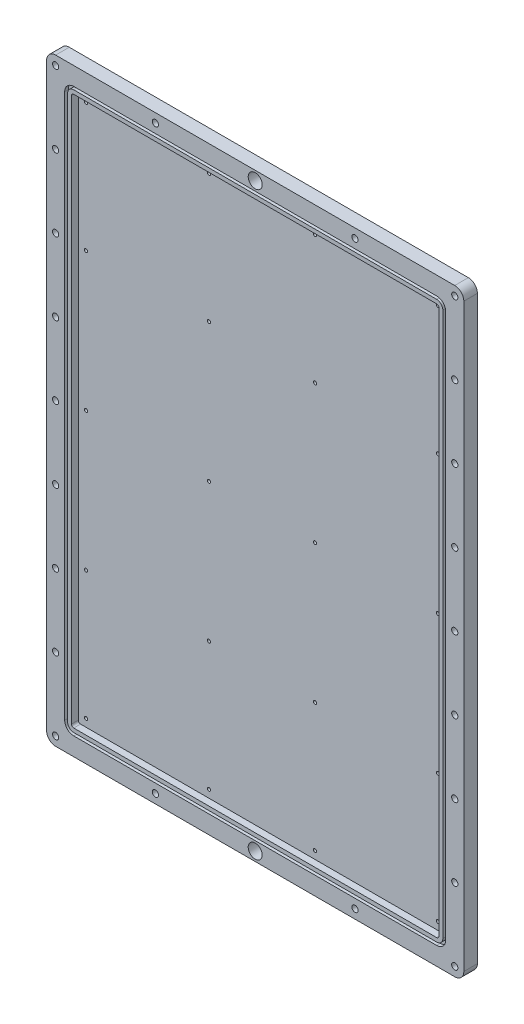
SolidWorks part; units mm, degrees
ref_plane "Front Plane" through (0, 0, 0) normal (0, 0, 1) x (1, 0, 0)
ref_plane "Top Plane" through (0, 0, 0) normal (0, 1, 0) x (1, 0, 0)
ref_plane "Right Plane" through (0, 0, 0) normal (1, 0, 0) x (0, 0, -1)
sketch "Sketch1" plane through (0, 0, 0) normal (0, 0, 1) x (1, 0, 0)
  line L1 (0, 0) -> (292.0492, 0)
  line L2 (0, 0) -> (0, 419.0492)
  line L3 (0, 419.0492) -> (292.0492, 419.0492)
  line L4 (292.0492, 0) -> (292.0492, 419.0492)
  dimension "D1" = 419.0492
  dimension "D2" = 292.0492
extrude "Boss-Extrude1" add sketch "Sketch1" along normal blind 9.525
sketch "Sketch4" plane through (0, 0, 9.525) normal (0, 0, 1) x (1, 0, 0)
  line L0 (91.477, 6.3246) -> (91.477, 0) construction
  line L1 (0, 0) -> (292.0492, 0) construction
  line L2 (6.3246, 94.9672) -> (0, 94.9672) construction
  line L4 (6.3246, 412.7246) -> (285.7246, 412.7246) construction
  line L5 (6.3246, 412.7246) -> (6.3246, 6.3246) construction
  line L6 (6.3246, 6.3246) -> (285.7246, 6.3246) construction
  line L7 (285.7246, 412.7246) -> (285.7246, 6.3246) construction
  line L11 (0, 419.0492) -> (0, 0) construction
  line L12 (285.7246, 110.613) -> (292.0492, 110.613) construction
  line L13 (292.0492, 0) -> (292.0492, 419.0492) construction
  line L14 (125.5626, 412.7246) -> (125.5626, 419.0492) construction
  line L15 (292.0492, 419.0492) -> (0, 419.0492) construction
  circle A0 centre (6.3246, 6.3246) radius 2.1844
  circle A1 centre (6.3246, 412.7246) radius 2.1844
  circle A2 centre (285.7246, 412.7246) radius 2.1844
  circle A3 centre (285.7246, 6.3246) radius 2.1844
  dimension "D5" = 4.3688
  dimension "D1" = 279.4
  dimension "D2" = 406.4
extrude "Cut-Extrude1" cut sketch "Sketch4" against normal through all
sketch "Sketch5" plane through (0, 0, 9.525) normal (0, 0, 1) x (1, 0, 0)
  line L0 (0, 209.5246) -> (12.6746, 209.5246) construction
  line L1 (19.0246, 406.3746) -> (273.0246, 406.3746)
  line L2 (12.6746, 400.0246) -> (12.6746, 19.0246)
  line L3 (19.0246, 12.6746) -> (273.0246, 12.6746)
  line L4 (279.3746, 400.0246) -> (279.3746, 19.0246)
  line L5 (0, 419.0492) -> (0, 0) construction
  line L6 (279.3746, 209.5246) -> (292.0492, 209.5246) construction
  line L8 (19.0246, 14.7066) -> (273.0246, 14.7066)
  line L9 (14.7066, 400.0246) -> (14.7066, 19.0246)
  line L10 (19.0246, 404.3426) -> (273.0246, 404.3426)
  line L11 (277.3426, 400.0246) -> (277.3426, 19.0246)
  line L12 (292.0492, 0) -> (292.0492, 419.0492) construction
  line L13 (146.0246, 12.6746) -> (146.0246, 0) construction
  line L14 (0, 0) -> (292.0492, 0) construction
  line L15 (146.0246, 406.3746) -> (146.0246, 419.0492) construction
  line L16 (292.0492, 419.0492) -> (0, 419.0492) construction
  arc A0 (273.0246, 12.6746) -> (279.3746, 19.0246) centre (273.0246, 19.0246) ccw
  arc A1 (12.6746, 19.0246) -> (19.0246, 12.6746) centre (19.0246, 19.0246) ccw
  arc A2 (273.0246, 406.3746) -> (279.3746, 400.0246) centre (273.0246, 400.0246) cw
  arc A3 (19.0246, 406.3746) -> (12.6746, 400.0246) centre (19.0246, 400.0246) ccw
  arc A4 (14.7066, 19.0246) -> (19.0246, 14.7066) centre (19.0246, 19.0246) ccw
  arc A5 (19.0246, 404.3426) -> (14.7066, 400.0246) centre (19.0246, 400.0246) ccw
  arc A6 (273.0246, 404.3426) -> (277.3426, 400.0246) centre (273.0246, 400.0246) cw
  arc A7 (273.0246, 14.7066) -> (277.3426, 19.0246) centre (273.0246, 19.0246) ccw
  dimension "D5" = 6.35
  dimension "D1" = 266.7
  dimension "D2" = 393.7
  dimension "D6" = 2.032
  dimension "D7" = 2.032
extrude "Cut-Extrude2" cut sketch "Sketch5" against normal blind 2.54 contours L1 A3 L2 A1 L3 A0 L4 A2 A7 L8 A4 L9 A5 L10 A6 L11 region at (146.0246, 405.8991, 9.525)
pattern_linear "LPattern3" count 4 spacing 69.85 along (1, 0, 0) of face at (8.509, 412.7246, 0) of face at (8.509, 6.3246, 0)
pattern_linear "LPattern4" count 8 spacing 50.8 along (0, -1, 0) of face at (8.509, 412.7246, 0) of face at (287.909, 412.7246, 0)
sketch "Sketch6" plane through (0, 0, 9.525) normal (0, 0, 1) x (1, 0, 0)
  line L4 (274.6121, 19.0246) -> (274.6121, 400.0246)
  line L5 (274.6121, 19.0246) -> (274.6121, 400.0246)
  line L6 (273.0246, 401.6121) -> (19.0246, 401.6121)
  line L7 (273.0246, 401.6121) -> (19.0246, 401.6121)
  line L8 (17.4371, 400.0246) -> (17.4371, 19.0246)
  line L9 (17.4371, 400.0246) -> (17.4371, 19.0246)
  line L10 (19.0246, 17.4371) -> (273.0246, 17.4371)
  line L11 (19.0246, 17.4371) -> (273.0246, 17.4371)
  arc A4 (273.0246, 17.4371) -> (274.6121, 19.0246) centre (273.0246, 19.0246) ccw
  arc A5 (273.0246, 17.4371) -> (274.6121, 19.0246) centre (273.0246, 19.0246) ccw
  arc A6 (274.6121, 400.0246) -> (273.0246, 401.6121) centre (273.0246, 400.0246) ccw
  arc A7 (274.6121, 400.0246) -> (273.0246, 401.6121) centre (273.0246, 400.0246) ccw
  arc A8 (19.0246, 401.6121) -> (17.4371, 400.0246) centre (19.0246, 400.0246) ccw
  arc A9 (19.0246, 401.6121) -> (17.4371, 400.0246) centre (19.0246, 400.0246) ccw
  arc A10 (17.4371, 19.0246) -> (19.0246, 17.4371) centre (19.0246, 19.0246) ccw
  arc A11 (17.4371, 19.0246) -> (19.0246, 17.4371) centre (19.0246, 19.0246) ccw
  dimension "D1" = 2.7305
extrude "Cut-Extrude3" cut sketch "Sketch6" against normal blind 4.7625
sketch "Sketch7" plane through (0, 0, 4.7625) normal (0, 0, 1) x (1, 0, 0)
  line L0 (273.0246, 401.6121) -> (19.0246, 401.6121) construction
  line L1 (22.8346, 396.2146) -> (269.2146, 396.2146) construction
  line L2 (22.8346, 396.2146) -> (22.8346, 22.8346) construction
  line L3 (22.8346, 22.8346) -> (269.2146, 22.8346) construction
  line L4 (269.2146, 396.2146) -> (269.2146, 22.8346) construction
  line L5 (17.4371, 400.0246) -> (17.4371, 19.0246) construction
  line L6 (274.6121, 19.0246) -> (274.6121, 400.0246) construction
  line L7 (269.2146, 112.649) -> (22.8346, 112.649) construction
  line L8 (17.4371, 400.0246) -> (17.4371, 19.0246) construction
  line L9 (274.6121, 19.0246) -> (274.6121, 400.0246) construction
  line L10 (269.2146, 209.5246) -> (22.8346, 209.5246) construction
  line L11 (183.1594, 396.2146) -> (183.1594, 22.8346) construction
  line L12 (108.8898, 22.8346) -> (108.8898, 396.2146) construction
  line L13 (269.2146, 306.4002) -> (22.8346, 306.4002) construction
  line L16 (19.0246, 17.4371) -> (273.0246, 17.4371) construction
  circle A0 centre (22.8346, 396.2146) radius 1.1303
  circle A1 centre (269.2146, 396.2146) radius 1.1303
  circle A2 centre (22.8346, 22.8346) radius 1.1303
  circle A3 centre (108.8898, 22.8346) radius 1.1303
  circle A4 centre (108.8898, 396.2146) radius 1.1303
  circle A5 centre (183.1594, 396.2146) radius 1.1303
  circle A6 centre (183.1594, 22.8346) radius 1.1303
  circle A7 centre (269.2146, 22.8346) radius 1.1303
  circle A8 centre (269.2146, 112.649) radius 1.1303
  circle A9 centre (108.8898, 112.649) radius 1.1303
  circle A10 centre (183.1594, 112.649) radius 1.1303
  circle A11 centre (22.8346, 112.649) radius 1.1303
  circle A12 centre (269.2146, 209.5246) radius 1.1303
  circle A13 centre (108.8898, 209.5246) radius 1.1303
  circle A14 centre (183.1594, 209.5246) radius 1.1303
  circle A15 centre (22.8346, 209.5246) radius 1.1303
  circle A16 centre (269.2146, 306.4002) radius 1.1303
  circle A17 centre (108.8898, 306.4002) radius 1.1303
  circle A18 centre (183.1594, 306.4002) radius 1.1303
  circle A19 centre (22.8346, 306.4002) radius 1.1303
  dimension "D5" = 2.2606
  dimension "D11" = 96.8756
  dimension "D9" = 373.38
  dimension "D13" = 86.0552
  dimension "D14" = 86.0552
  dimension "D1" = 5.3975
  dimension "D2" = 5.3975
  dimension "D3" = 5.3975
  dimension "D4" = 5.3975
  dimension "D6" = 91.4527
  dimension "D7" = 91.4527
  dimension "D8" = 91.4527
  dimension "D10" = 96.8756
  dimension "D12" = 91.4527
extrude "Cut-Extrude4" cut sketch "Sketch7" against normal blind 3.175
sketch "Sketch8" plane through (0, 0, 9.525) normal (0, 0, 1) x (1, 0, 0)
  circle A0 centre (146.0246, 412.7246) radius 4.9022
  circle A1 centre (146.0246, 6.3246) radius 4.9022
  dimension "D1" = 9.8044
extrude "Cut-Extrude5" cut sketch "Sketch8" against normal through all
fillet "Fillet1" radius 6.35 4 edges at (292.0492, 0, 4.7625) (0, 0, 4.7625) (292.0492, 419.0492, 4.7625) (0, 419.0492, 4.7625)
chamfer "Chamfer1" distance 2.54 angle 41 22 edges at (78.359, 412.7246, 0) (218.059, 412.7246, 0) (287.909, 412.7246, 0) (287.909, 361.9246, 0) (287.909, 311.1246, 0) (287.909, 260.3246, 0) (287.909, 209.5246, 0) (287.909, 158.7246, 0) (287.909, 107.9246, 0) (287.909, 57.1246, 0) (287.909, 6.3246, 0) (218.059, 6.3246, 0) (78.359, 6.3246, 0) (8.509, 6.3246, 0) (8.509, 57.1246, 0) (8.509, 107.9246, 0) (8.509, 158.7246, 0) (8.509, 260.3246, 0) (8.509, 311.1246, 0) (8.509, 412.7246, 0) (8.509, 361.9246, 0) (8.509, 209.5246, 0) first distance on face at (78.359, 412.7246, 0) first distance on face at (218.059, 412.7246, 0) first distance on face at (287.909, 412.7246, 0) first distance on face at (287.909, 361.9246, 0) first distance on face at (287.909, 311.1246, 0) first distance on face at (287.909, 260.3246, 0) first distance on face at (287.909, 209.5246, 0) first distance on face at (287.909, 158.7246, 0) first distance on face at (287.909, 107.9246, 0) first distance on face at (287.909, 57.1246, 0) first distance on face at (287.909, 6.3246, 0) first distance on face at (218.059, 6.3246, 0) first distance on face at (78.359, 6.3246, 0) first distance on face at (8.509, 6.3246, 0) first distance on face at (8.509, 57.1246, 0) first distance on face at (8.509, 107.9246, 0) first distance on face at (8.509, 158.7246, 0) first distance on face at (8.509, 260.3246, 0) first distance on face at (8.509, 311.1246, 0) first distance on face at (8.509, 412.7246, 0) first distance on face at (8.509, 361.9246, 0) first distance on face at (8.509, 209.5246, 0)
